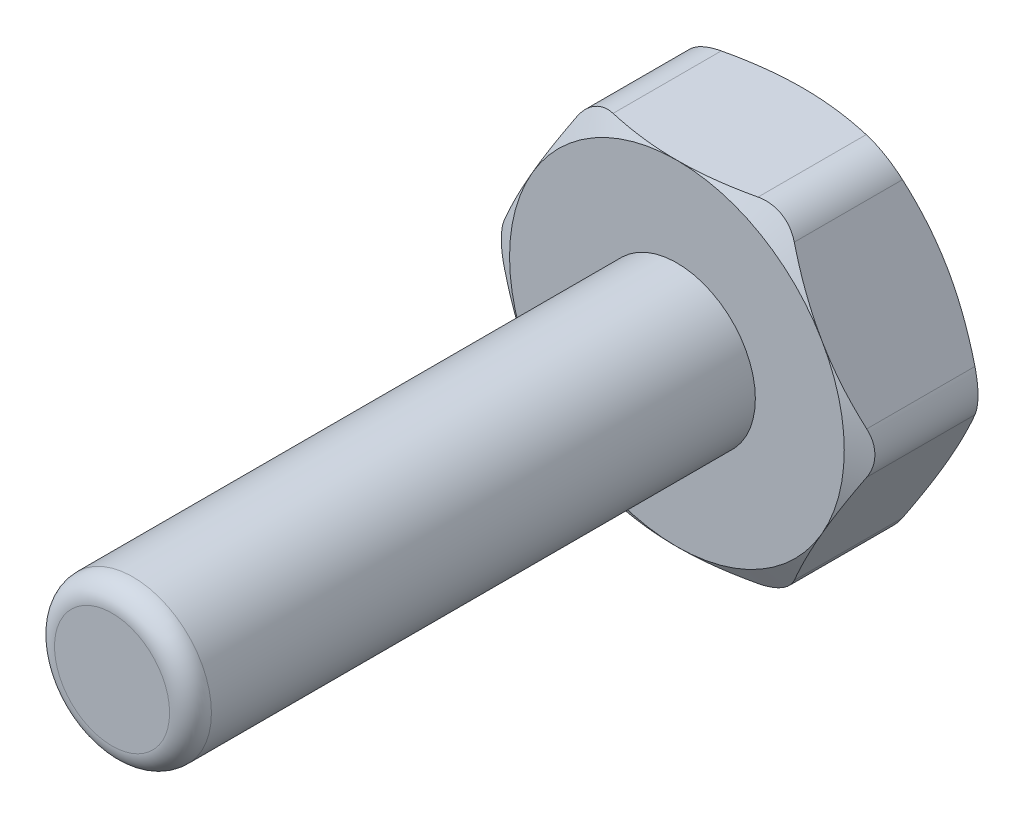
SolidWorks part; units mm, degrees
ref_plane "Front Plane" through (0, 0, 0) normal (0, 0, 1) x (1, 0, 0)
ref_plane "Top Plane" through (0, 0, 0) normal (0, 1, 0) x (1, 0, 0)
ref_plane "Right Plane" through (0, 0, 0) normal (1, 0, 0) x (0, 0, -1)
sketch "Sketch4" plane through (0, 0, 0) normal (0, 0, 1) x (1, 0, 0)
  line L1 (-2.3094, 4) -> (-4.6188, 0)
  line L2 (-4.6188, 0) -> (-2.3094, -4)
  line L3 (-2.3094, -4) -> (2.3094, -4)
  line L4 (2.3094, -4) -> (4.6188, 0)
  line L5 (4.6188, 0) -> (2.3094, 4)
  line L6 (2.3094, 4) -> (-2.3094, 4)
  circle A0 centre (0, 0) radius 4 construction
  circle A1 centre (0, 0) radius 1.875
  dimension "D1" = 3.75
  dimension "D2" = 8
extrude "Boss-Extrude2" add sketch "Sketch4" along normal mid plane 3 contours A1 | L5 L6 L1 L2 L3 L4 A1 region at (0, 3.8778, 0) region at (0, 0, 0)
sketch "Sketch5" plane through (0, 0, 1.5) normal (0, 0, 1) x (1, 0, 0)
  circle A0 centre (0, 0) radius 4 construction
  circle A1 centre (0, 0) radius 4
extrude "Cut-Extrude1" cut sketch "Sketch5" against normal blind 15 draft 60 flip side to cut
mirror "Mirror1" about plane through (0, 0, 0) normal (0, 0, 1) of "Cut-Extrude1"
extrude "Boss-Extrude3" add sketch "Sketch4<3>" along normal blind 15 contours A1
sketch "Sketch4<3>" plane through (0, 0, 0) normal (0, 0, 1) x (1, 0, 0) same geometry as "Sketch4"
fillet "Fillet1" radius 1 6 edges at (4.6188, 0, 0) (2.3094, -4, 0) (-2.3094, -4, 0) (-4.6188, 0, 0) (-2.3094, 4, 0) (2.3094, 4, 0)
fillet "Fillet2" radius 0.5 1 edges at (1.875, 0, 15)
